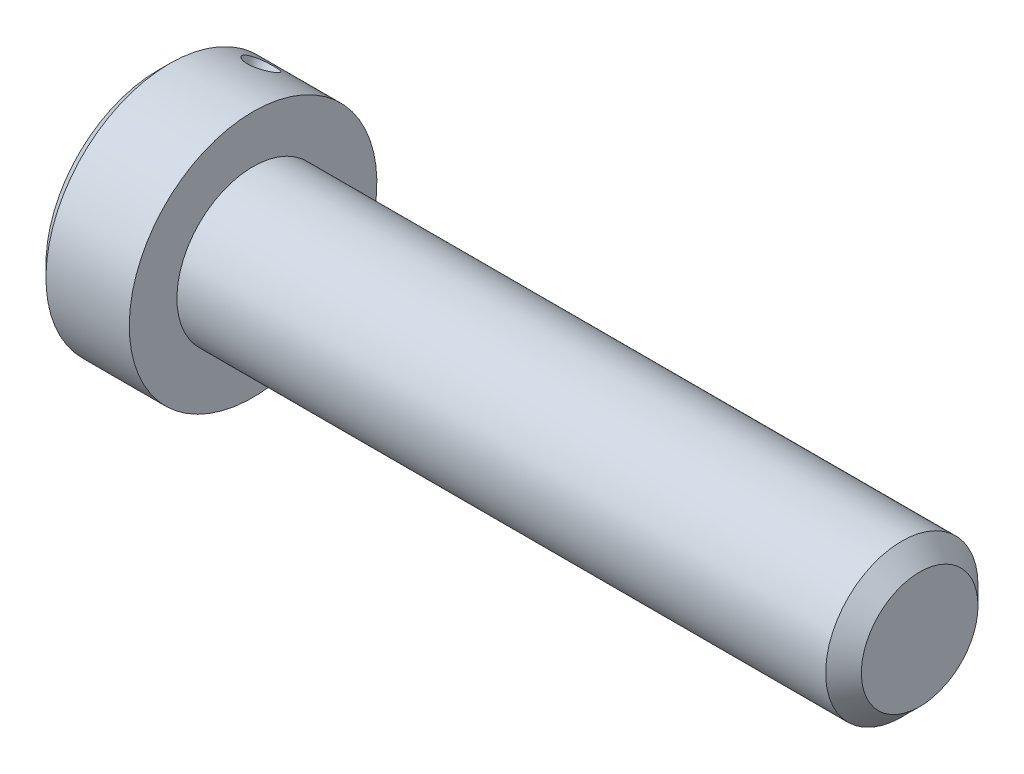
SolidWorks part; units mm, degrees
material "Alloy Steel"
ref_plane "Front Plane" through (0, 0, 0) normal (0, 0, 1) x (1, 0, 0)
ref_plane "Top Plane" through (0, 0, 0) normal (0, 1, 0) x (1, 0, 0)
ref_plane "Right Plane" through (0, 0, 0) normal (1, 0, 0) x (0, 0, -1)
sketch "Sketch1" plane through (0, 0, 0) normal (0, 0, 1) x (1, 0, 0)
  line L0 (17.5, 0) -> (-17.5, 0) construction
  line L1 (17.5, 4) -> (17.5, -4) construction
  line L2 (-17.5, 6.5) -> (-17.5, -6.5) construction
  line L3 (-17.5, 6.5) -> (-21.875, 6.5) construction
  line L4 (-21.875, 6.5) -> (-22.5, 5.875) construction
  line L5 (-22.5, 5.875) -> (-22.5, -5.875) construction
  line L6 (-22.5, -5.875) -> (-21.875, -6.5) construction
  line L7 (-21.875, -6.5) -> (-17.5, -6.5) construction
  line L8 (-4.5, 4) -> (-4.5, -4) construction
  point P7 (-18.55, 0)
  point P12 (12.5, -4)
  dimension "D1" = 45
  dimension "Dec." = 8
  dimension "Length" = 35
  dimension "Head Dia" = 13
  dimension "Head Height" = 5
  dimension "Hex Depth" = 3.95
  dimension "Chamfer" = 0.625
  dimension "D2" = 5
  dimension "Thread Length" = 22
ref_plane "Plane1" through (17.5, 0, 0) normal (1, 0, 0) x (0, 0, -1)
ref_plane "Plane2" through (-22.5, 0, 0) normal (1, 0, 0) x (0, 0, -1)
sketch "Sketch2" plane through (17.5, 0, 0) normal (1, 0, 0) x (0, 0, -1)
  circle A0 centre (0, 0) radius 4
extrude "Boss-Extrude1" add sketch "Sketch2" against normal up to vertex (22 mm away) up to point (-4.5, 4, 0)
sketch "Sketch3" plane through (17.5, 0, 0) normal (1, 0, 0) x (0, 0, -1)
  circle A0 centre (0, 0) radius 4 construction
  circle A1 centre (0, 0) radius 4
curve "Helix/Spiral1" pitch 1.25 height 23.25 turns 18.6 parameters "Pitch"=1.25
chamfer "Chamfer1" distance 0.9375 angle 45 1 edges at (17.5, 0, -4)
sketch "Sketch5" plane through (0, 0, 0) normal (0, 0, 1) x (1, 0, 0)
  line L0 (16.9531, 4) -> (18.0469, 4)
  line L1 (18.0469, 4) -> (17.5781, 3.1881)
  line L2 (17.5781, 3.1881) -> (17.4219, 3.1881)
  line L3 (17.4219, 3.1881) -> (16.9531, 4)
  line L4 (17.5, 3.1881) -> (17.5, 4) construction
  line L5 (17.1875, 3.5941) -> (17.8125, 3.5941) construction
  dimension "D1" = 60
  dimension "D2" = 0.625
  dimension "D3" = 0.1562
sweep "Cut-Sweep1" [suppressed] cut profiles "Sketch5" path "Helix/Spiral1"
sketch "Sketch4" plane through (-22.5, 0, 0) normal (1, 0, 0) x (0, 0, -1)
  line L0 (-6.5, 0.7937) -> (6.5, 0.7937) construction
  line L1 (0, 2.8868) -> (-2.5, 1.4434)
  line L2 (-2.5, 1.4434) -> (-2.5, -1.4434)
  line L3 (-2.5, -1.4434) -> (0, -2.8868)
  line L4 (0, -2.8868) -> (2.5, -1.4434)
  line L5 (2.5, -1.4434) -> (2.5, 1.4434)
  line L6 (2.5, 1.4434) -> (0, 2.8868)
  line L7 (0, 0) -> (0, 0.7937) construction
  circle A0 centre (0, 0) radius 2.5 construction
  dimension "Hex Size" = 5
  dimension "D1" = 13
  dimension "D2" = 0.7937
sketch "Sketch10" plane through (0, 0, 0) normal (0, 0, 1) x (1, 0, 0)
  line L0 (-17.5, 0) -> (-2.1906, 0) construction
  line L1 (-2.1906, 0) -> (-4.5, 4)
  line L2 (-4.5, 4) -> (-17.5, 4)
  line L3 (-17.5, 4) -> (-17.5, 0)
  line L4 (-17.5, 6.5) -> (-17.5, -6.5) construction
  line L5 (-17.5, 0) -> (-2.1906, 0)
  dimension "D1" = 60
revolve "Revolve2" add sketch "Sketch10" angle 360 about L0
sketch "Sketch6" plane through (0, 0, 0) normal (0, 0, 1) x (1, 0, 0)
  line L0 (-21.875, 6.5) -> (-22.5, 5.875) construction
  line L1 (-17.5, 6.5) -> (-21.875, 6.5) construction
  line L2 (-17.5, 6.5) -> (-17.5, -6.5) construction
  line L3 (-22.5, 5.875) -> (-22.5, -5.875) construction
  line L4 (-21.875, 6.5) -> (-22.5, 5.875)
  line L5 (-17.5, 6.5) -> (-21.875, 6.5)
  line L6 (-17.5, 6.5) -> (-17.5, 0)
  line L7 (-22.5, 5.875) -> (-22.5, 0)
  line L8 (-17.5, 0) -> (-22.5, 0) construction
  line L9 (-17.5, 0) -> (-22.5, 0)
revolve "Revolve1" add sketch "Sketch6" angle 360 about L8
extrude "Cut-Extrude1" cut sketch "Sketch4" along normal up to vertex (3.95 mm away) up to point (-18.55, 0, 0)
sketch "Sketch8" plane through (-22.5, 0, 0) normal (-1, 0, 0) x (0, 0, 1)
  circle A1 centre (0, 0) radius 2.8868
extrude "Cut-Extrude2" cut sketch "Sketch8" against normal through all draft 45
sketch "Sketch11" plane through (0, 2.1651, -1.25) normal (0, -0.866, 0.5) x (1, 0, 0)
  line L3 (-22.1132, 0) -> (-18.55, 0) construction
  line L4 (-18.55, -1.4434) -> (-18.55, 1.4434) construction
  circle A0 centre (-20.3316, 0) radius 0.7937
  spline S0 degree 3 poles (-22.5, -1.4434) (-22.3872, -1.2178) (-22.2913, -0.9872) (-22.1886, -0.6289) (-22.1613, -0.5073) (-22.1236, -0.2591) (-22.1135, -0.1313) (-22.1127, 0.2467) (-22.1509, 0.4944) (-22.2893, 0.9829) (-22.3866, 1.2165) (-22.5, 1.4434) knots 0 0 0 0 0.25 0.25 0.375 0.375 0.5 0.5 0.75 0.75 1 1 1 1 construction
  point P15 (-20.3316, 0)
  dimension "D1" = 1.5875
extrude "Cut-Extrude3" cut sketch "Sketch11" against normal through all both and the other way through all contours A0 | A0 region at (-20.3316, 2.1651, -1.25)
equation "\"D3@Helix/Spiral1\" = \"Thread Length@Sketch1\"+\"Pitch@Helix/Spiral1\""
equation "\"D3@Sketch5\" = \"Pitch@Helix/Spiral1\"*.125"
equation "\"D2@Sketch5\" = \"Pitch@Helix/Spiral1\"*.50"
equation "\"D1@Chamfer1\" = \"Pitch@Helix/Spiral1\"*.75"
equation "\"D2@Sketch1\" = \"Pitch@Helix/Spiral1\"*4"
equation "\"D1@Sketch4\" = \"Head Dia@Sketch1\""
equation "\"Chamfer@Sketch1\" = \"Head Height@Sketch1\"/8"
